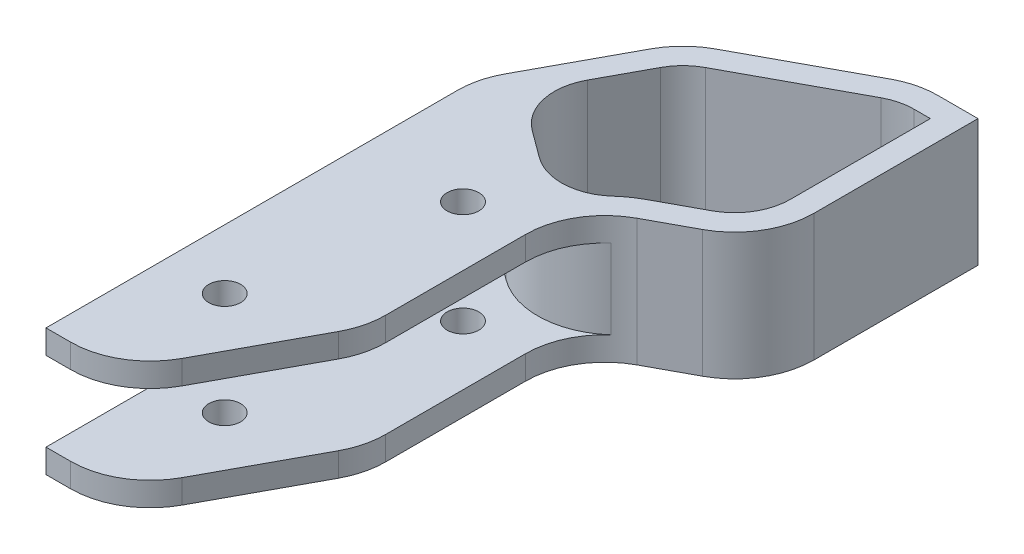
SolidWorks part; units mm, degrees
ref_plane "Front Plane" through (0, 0, 0) normal (0, 0, 1) x (1, 0, 0)
ref_plane "Top Plane" through (0, 0, 0) normal (0, 1, 0) x (1, 0, 0)
ref_plane "Right Plane" through (0, 0, 0) normal (1, 0, 0) x (0, 0, -1)
sketch "Sketch1" plane through (0, 0, 0) normal (0, 1, 0) x (1, 0, 0)
  line L0 (1.5605, -15) -> (12.5, 5.2321)
  line L1 (12.5, 5.2321) -> (12.5, 31.3289)
  line L2 (12.5, 31.3289) -> (28.35, 39.8989)
  line L3 (28.35, 39.8989) -> (28.35, 66.4967)
  line L4 (28.35, 66.4967) -> (20.7562, 66.4967)
  line L5 (20.7562, 66.4967) -> (1.5605, 56.1176)
  line L6 (1.5605, 56.1176) -> (-7.5, 39.3605)
  line L7 (-7.5, 39.3605) -> (-7.5, -15)
  line L8 (-7.5, -15) -> (1.5605, -15)
  circle A0 centre (0, 0) radius 2
  circle A1 centre (5, 25) radius 2
  point P8 (9.0613, 39.3652)
  point P15 (2.1026, 49.2064)
  point P16 (23.7898, 66.3357)
  point P17 (0, 0)
  point P18 (0, 0)
  point P19 (0, 0)
  point P20 (2.0996, 25)
  point P21 (23.5603, 61.7197)
  point P22 (23.184, 66.4967)
  point P23 (1.5605, 54.3006)
  point P24 (0, 0)
  point P25 (-7.5, 40.4673)
  point P26 (1.5605, 56.1176)
  dimension "D1" = 4
  dimension "D2" = 25
  dimension "D3" = 28.4
  dimension "D4" = 7.5
  dimension "D5" = 5
  dimension "D6" = 7.5
  dimension "D7" = 15
  dimension "D8" = 61.6
  dimension "D9" = 23.35
extrude "Boss-Extrude1" add sketch "Sketch1" along normal blind 3
fillet "Fillet1" radius 10 7 edges at (20.7562, 1.5, -66.4967) (28.35, 1.5, -39.8989) (1.5605, 1.5, -56.1176) (-7.5, 1.5, -39.3605) (1.5605, 1.5, 15) (12.5, 1.5, -5.2321) (12.5, 1.5, -31.3289)
sketch "Sketch2" plane through (0, 3, 0) normal (0, 1, 0) x (1, 0, 0)
  line L0 (-0.2121, 34.7338) -> (3.2166, 32.2076)
  line L1 (1.5674, 37.149) -> (4.9961, 34.6228)
  line L2 (16.3169, 36.8031) -> (21.6794, 39.7026)
  line L3 (25.35, 45.8601) -> (25.35, 63.4967)
  line L4 (25.35, 63.4967) -> (23.2866, 63.4967)
  line L5 (19.9572, 62.6542) -> (5.6098, 54.8966)
  line L6 (2.7816, 52.0684) -> (-0.438, 46.1139)
  line L7 (0.1426, 53.4953) -> (-6.2965, 41.5863) construction
  line L8 (-3.0769, 47.5408) -> (-6.2965, 41.5863)
  line L9 (28.35, 66.4967) -> (23.2866, 66.4967)
  line L10 (18.5304, 65.2932) -> (4.1829, 57.5355)
  line L11 (0.1426, 53.4953) -> (-6.2965, 41.5863)
  line L12 (-7.5, 36.8301) -> (-7.5, -15)
  line L13 (-7.5, -15) -> (-4.4007, -15)
  line L14 (4.3958, -9.7562) -> (11.2965, 3.0063)
  line L15 (12.5, 7.7625) -> (12.5, 25.3677)
  line L16 (17.7438, 34.1642) -> (23.1062, 37.0636)
  line L17 (28.35, 45.8601) -> (28.35, 66.4967)
  line L18 (28.35, 66.4967) -> (23.2866, 66.4967)
  line L19 (18.5304, 65.2932) -> (4.1829, 57.5355)
  line L20 (0.1426, 53.4953) -> (-3.0769, 47.5408)
  line L21 (-7.5, 36.8301) -> (-7.5, -15)
  line L22 (-7.5, -15) -> (-4.4007, -15)
  line L23 (4.3958, -9.7562) -> (11.2965, 3.0063)
  line L24 (12.5, 7.7625) -> (12.5, 25.3677)
  line L25 (17.7438, 34.1642) -> (23.1062, 37.0636)
  line L26 (28.35, 45.8601) -> (28.35, 66.4967)
  arc A0 (-3.0769, 47.5408) -> (-0.2121, 34.7338) centre (5.7196, 42.7846) ccw
  arc A1 (15.8241, 32.813) -> (3.2166, 32.2076) centre (9.1483, 40.2583) cw
  arc A2 (-0.438, 46.1139) -> (1.5674, 37.149) centre (5.7196, 42.7846) ccw
  arc A3 (13.8214, 35.0466) -> (4.9961, 34.6228) centre (9.1483, 40.2583) cw
  arc A4 (16.3169, 36.8031) -> (13.8214, 35.0466) centre (22.5, 25.3677) ccw
  arc A5 (21.6794, 39.7026) -> (25.35, 45.8601) centre (18.35, 45.8601) ccw
  arc A6 (23.2866, 63.4967) -> (19.9572, 62.6542) centre (23.2866, 56.4967) ccw
  arc A7 (23.2866, 66.4967) -> (18.5304, 65.2932) centre (23.2866, 56.4967) ccw
  arc A8 (4.1829, 57.5355) -> (0.1426, 53.4953) centre (8.9391, 48.739) ccw
  arc A9 (-6.2965, 41.5863) -> (-7.5, 36.8301) centre (2.5, 36.8301) ccw
  arc A10 (-4.4007, -15) -> (4.3958, -9.7562) centre (-4.4007, -5) ccw
  arc A11 (11.2965, 3.0063) -> (12.5, 7.7625) centre (2.5, 7.7625) ccw
  arc A12 (17.7438, 34.1642) -> (12.5, 25.3677) centre (22.5, 25.3677) ccw
  arc A13 (23.1062, 37.0636) -> (28.35, 45.8601) centre (18.35, 45.8601) ccw
  arc A14 (23.2866, 66.4967) -> (18.5304, 65.2932) centre (23.2866, 56.4967) ccw
  arc A15 (4.1829, 57.5355) -> (0.1426, 53.4953) centre (8.9391, 48.739) ccw
  arc A16 (-6.2965, 41.5863) -> (-7.5, 36.8301) centre (2.5, 36.8301) ccw
  arc A17 (-4.4007, -15) -> (4.3958, -9.7562) centre (-4.4007, -5) ccw
  arc A18 (11.2965, 3.0063) -> (12.5, 7.7625) centre (2.5, 7.7625) ccw
  arc A19 (17.7438, 34.1642) -> (15.8241, 32.813) centre (22.5, 25.3677) ccw
  arc A20 (23.1062, 37.0636) -> (28.35, 45.8601) centre (18.35, 45.8601) ccw
  arc A21 (5.6098, 54.8966) -> (2.7816, 52.0684) centre (8.9391, 48.739) ccw
  arc A22 (17.7438, 34.1642) -> (12.5, 25.3677) centre (22.5, 25.3677) ccw construction
  arc A23 (17.7438, 34.1642) -> (12.5, 25.3677) centre (22.5, 25.3677) ccw
  circle A24 centre (0, 0) radius 2 construction
  circle A25 centre (5, 25) radius 2 construction
  circle A26 centre (0, 0) radius 2
  circle A27 centre (5, 25) radius 2
  circle A28 centre (5, 25) radius 5 construction
  point P50 (-3.0769, 47.5408)
  circle M19 centre (0, 0) radius 2
  line M20 (28.35, 66.4967) -> (23.2866, 66.4967)
  arc M21 (23.2866, 66.4967) -> (18.5304, 65.2932) centre (23.2866, 56.4967) ccw
  line M22 (18.5304, 65.2932) -> (4.1829, 57.5355)
  arc M23 (4.1829, 57.5355) -> (0.1426, 53.4953) centre (8.9391, 48.739) ccw
  line M24 (0.1426, 53.4953) -> (-6.2965, 41.5863)
  arc M25 (-6.2965, 41.5863) -> (-7.5, 36.8301) centre (2.5, 36.8301) ccw
  line M26 (-7.5, 36.8301) -> (-7.5, -15)
  line M27 (-7.5, -15) -> (-4.4007, -15)
  arc M28 (-4.4007, -15) -> (4.3958, -9.7562) centre (-4.4007, -5) ccw
  line M29 (4.3958, -9.7562) -> (11.2965, 3.0063)
  arc M30 (11.2965, 3.0063) -> (12.5, 7.7625) centre (2.5, 7.7625) ccw
  line M31 (12.5, 7.7625) -> (12.5, 25.3677)
  arc M32 (12.5, 25.3677) -> (17.7438, 34.1642) centre (22.5, 25.3677) cw
  line M33 (17.7438, 34.1642) -> (23.1062, 37.0636)
  arc M34 (23.1062, 37.0636) -> (28.35, 45.8601) centre (18.35, 45.8601) ccw
  line M35 (28.35, 45.8601) -> (28.35, 66.4967)
  circle M36 centre (5, 25) radius 2
  dimension "D2" = 10
  dimension "D4" = 10
  dimension "D1" = 0
  dimension "D3" = 3
extrude "Boss-Extrude2" add sketch "Sketch2" along normal blind 10 contours A1 A0 L0 A21 L5 A6 L3 A5 L2 A4 A3 L1 A2 L6 M32 M33 M34 M35 M20 M21 M22 M23 M24 region at (-3.5634, 3, -40.7081)
extrude "Boss-Extrude3" add sketch "Sketch2<3>" along normal blind 3 from surface contours A1 L0 A0 M32 M24 M25 M26 M27 M28 M29 M30 M31 M19 M36 | A1 A0 L0 A21 L5 A6 L3 A5 L2 A4 A3 L1 A2 L6 M32 M33 M34 M35 M20 M21 M22 M23 M24 region at (-3.5634, 3, -40.7081) region at (1.1829, 3, -12.4314) starting at face at (13.2679, 13, -47.4958)
sketch "Sketch2<3>" plane through (0, 3, 0) normal (0, 1, 0) x (1, 0, 0) same geometry as "Sketch2"
sketch "Sketch4" plane through (0, 3, 0) normal (0, 1, 0) x (1, 0, 0)
  line L5 (19.9572, 62.6542) -> (5.6098, 54.8966)
  line L6 (2.7816, 52.0684) -> (-0.438, 46.1139)
  line L7 (1.5674, 37.149) -> (4.9961, 34.6228)
  line L8 (16.3169, 36.8031) -> (21.6794, 39.7026)
  line L9 (25.35, 45.8601) -> (25.35, 63.4967)
  line L10 (19.9572, 62.6542) -> (5.6098, 54.8966)
  line L11 (2.7816, 52.0684) -> (-0.438, 46.1139)
  line L12 (1.5674, 37.149) -> (4.9961, 34.6228)
  line L13 (16.3169, 36.8031) -> (21.6794, 39.7026)
  line L14 (25.35, 45.8601) -> (25.35, 63.4967)
  line L16 (25.35, 63.4967) -> (23.2866, 63.4967)
  line L17 (25.35, 63.4967) -> (23.2866, 63.4967)
  arc A6 (5.6098, 54.8966) -> (2.7816, 52.0684) centre (8.9391, 48.739) ccw
  arc A7 (-0.438, 46.1139) -> (1.5674, 37.149) centre (5.7196, 42.7846) ccw
  arc A8 (4.9961, 34.6228) -> (13.8214, 35.0466) centre (9.1483, 40.2583) ccw
  arc A9 (16.3169, 36.8031) -> (13.8214, 35.0466) centre (22.5, 25.3677) ccw
  arc A10 (21.6794, 39.7026) -> (25.35, 45.8601) centre (18.35, 45.8601) ccw
  arc A11 (23.2866, 63.4967) -> (19.9572, 62.6542) centre (23.2866, 56.4967) ccw
  arc A12 (5.6098, 54.8966) -> (2.7816, 52.0684) centre (8.9391, 48.739) ccw
  arc A13 (-0.438, 46.1139) -> (1.5674, 37.149) centre (5.7196, 42.7846) ccw
  arc A14 (4.9961, 34.6228) -> (13.8214, 35.0466) centre (9.1483, 40.2583) ccw
  arc A15 (16.3169, 36.8031) -> (13.8214, 35.0466) centre (22.5, 25.3677) ccw
  arc A16 (21.6794, 39.7026) -> (25.35, 45.8601) centre (18.35, 45.8601) ccw
  arc A17 (23.2866, 63.4967) -> (19.9572, 62.6542) centre (23.2866, 56.4967) ccw
  dimension "D1" = 0
extrude "Cut-Extrude1" cut sketch "Sketch4" against normal through all
